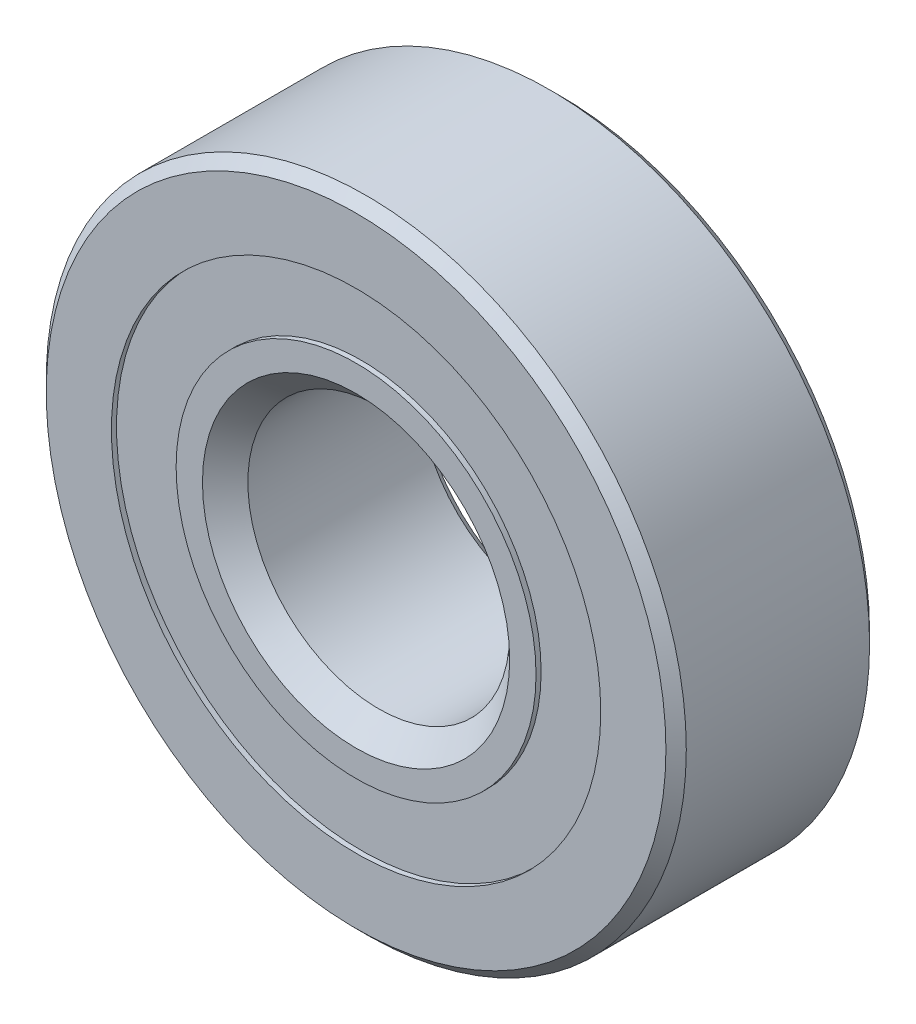
SolidWorks part; units mm, degrees
ref_plane "Front Plane" through (0, 0, 0) normal (0, 0, 1) x (1, 0, 0)
ref_plane "Top Plane" through (0, 0, 0) normal (0, 1, 0) x (1, 0, 0)
ref_plane "Right Plane" through (0, 0, 0) normal (1, 0, 0) x (0, 0, -1)
sketch "Sketch1" plane through (0, 0, 0) normal (1, 0, 0) x (0, 0, -1)
  line L0 (-5.5562, 0) -> (5.5562, 0) construction
  line L1 (0, 17.4625) -> (0, -17.4625) construction
  line L2 (5.0006, 17.4625) -> (-5.0006, 17.4625)
  line L3 (-5.0006, 17.4625) -> (-5.5563, 16.9069)
  line L4 (-5.5563, 16.9069) -> (-5.5563, 13.3498)
  line L5 (-5.5563, 13.3498) -> (-2.4694, 13.3498)
  line L6 (5.5562, 13.3498) -> (2.4694, 13.3498)
  line L7 (5.5562, 16.9069) -> (5.5562, 13.3498)
  line L8 (5.0006, 17.4625) -> (5.5562, 16.9069)
  line L9 (0, 17.4625) -> (0, 12.3031) construction
  line L10 (0, 12.3031) -> (0, 7.1437) construction
  arc A0 (-2.4694, 13.3498) -> (2.4694, 13.3498) centre (0, 12.3031) cw
  point P14 (0, 7.1437)
  dimension "Width" = 11.1125
  dimension "OD" = 34.925
  dimension "D1" = 45
  dimension "D2" = 0.5556
  dimension "D3" = 4.9389
  dimension "D4" = 1.0467
revolve "Revolve1" add sketch "Sketch1" angle 360 about L0
sketch "Sketch2" plane through (0, 0, 0) normal (1, 0, 0) x (0, 0, -1)
  line L0 (-5.2784, 11.2564) -> (-2.4694, 11.2564)
  line L1 (-5.5563, 16.9069) -> (-5.5563, -16.9069) construction
  line L2 (-5.5563, 9.8194) -> (-5.2784, 9.8194) construction
  line L3 (-5.2784, 9.5416) -> (-4.1192, 8.3824)
  line L4 (-4.1192, 8.3824) -> (0, 8.3824)
  line L5 (0, 17.4625) -> (0, -17.4625) construction
  line L6 (0, 8.3824) -> (0, 9.621)
  line L7 (0, 9.621) -> (0, 7.1437) construction
  line L8 (-5.5563, 11.2564) -> (-5.5563, 8.3824) construction
  line L9 (-5.5563, 8.3824) -> (-4.1192, 8.3824) construction
  line L10 (-5.2784, 11.2564) -> (-5.2784, 9.5416)
  line L11 (-5.2784, 11.2564) -> (-5.2784, 17.1847) construction
  line L12 (-5.0006, 17.4625) -> (-5.5563, 16.9069) construction
  arc A0 (-2.4694, 11.2564) -> (0, 9.621) centre (0, 12.3031) ccw
  arc A1 (2.4694, 13.3498) -> (-2.4694, 13.3498) centre (0, 12.3031) ccw construction
  circle A2 centre (0, 12.3031) radius 2.6821 construction
  dimension "D1" = 45
revolve "Revolve2" [suppressed] add sketch "Sketch2" angle 360 about L0
sketch "Sketch3" plane through (0, 0, 0) normal (1, 0, 0) x (0, 0, -1)
  line L0 (-5.2784, 9.5416) -> (-4.1192, 8.3824)
  line L1 (-4.1192, 8.3824) -> (0, 8.3824)
  line L2 (0, 8.3824) -> (0, 9.621)
  line L3 (-5.5563, 9.8194) -> (-5.5563, 8.3824)
  line L4 (-5.5563, 11.2564) -> (-5.5563, 8.3824) construction
  line L5 (-5.5563, 8.3824) -> (-4.3176, 7.1437)
  line L6 (-4.3176, 7.1437) -> (5.0006, 7.1437)
  line L7 (5.0006, 17.4625) -> (5.0006, -17.4625) construction
  line L8 (5.0006, 7.1437) -> (5.5562, 7.6994)
  line L9 (5.5562, -16.9069) -> (5.5562, 16.9069) construction
  line L10 (5.5562, 7.6994) -> (5.5562, 11.2564)
  line L11 (5.5562, 11.2564) -> (2.4694, 11.2564)
  line L12 (-5.5563, 9.8194) -> (-5.2784, 9.8194)
  line L13 (5.0006, 17.4625) -> (5.5562, 16.9069) construction
  line L14 (-5.2784, 9.8194) -> (-5.2784, 9.5416)
  circle A0 centre (0, 12.3031) radius 2.6821 construction
  arc A1 (2.4694, 11.2564) -> (0, 9.621) centre (0, 12.3031) cw
revolve "Revolve3" add sketch "Sketch3" angle 360 about L0
sketch "Sketch4" plane through (0, 0, 0) normal (1, 0, 0) x (0, 0, -1)
  line L0 (-2.6821, 12.3031) -> (2.6821, 12.3031)
  circle A1 centre (0, 12.3031) radius 2.6821 construction
  arc A2 (-2.6821, 12.3031) -> (2.6821, 12.3031) centre (0, 12.3031) cw
  arc A3 (2.4694, 13.3498) -> (-2.4694, 13.3498) centre (0, 12.3031) ccw construction
revolve "Revolve4" add sketch "Sketch4" angle 360 about L0
ref_axis "Axis1" through (0, 0, -5.5562) along (0, 0, 1)
pattern_circular "CirPattern1" count 12 every 30 about axis through (0, 0, -5.5562) along (0, 0, 1) of bodies 104
sketch "Sketch5" plane through (0, 0, 0) normal (1, 0, 0) x (0, 0, -1)
  line L0 (-5.5563, 13.3498) -> (-2.4694, 13.3498) construction
  line L1 (-5.2784, 13.3498) -> (-2.6821, 13.3498)
  line L2 (-5.2784, 13.3498) -> (-5.2784, 9.8194)
  line L3 (-5.2784, 9.8194) -> (-2.6821, 9.8194)
  line L4 (-2.6821, 13.3498) -> (-2.6821, 9.8194)
  line L6 (-5.0006, 17.4625) -> (-5.5563, 16.9069) construction
  line L7 (0, 17.4625) -> (0, 7.1437) construction
  line L8 (5.2784, 9.8194) -> (2.6821, 9.8194)
  line L9 (2.6821, 13.3498) -> (2.6821, 9.8194)
  line L10 (5.2784, 13.3498) -> (2.6821, 13.3498)
  line L11 (5.2784, 13.3498) -> (5.2784, 9.8194)
  circle A0 centre (0, 12.3031) radius 2.6821 construction
  point P10 (-5.2784, 17.1847)
revolve "Revolve5" add sketch "Sketch5" angle 360 about L0
equation "\"D2@Sketch1\" = \"Width@Sketch1\"*.05"
equation "\"D3@Sketch1\" = \"Width@Sketch1\"/2.25"
equation "\"D4@Sketch1\" = (((\"OD@Sketch1\"-\"Width@Sketch1\")/2)/3.25)/3.5"
equation "\"D2@CirPattern1\" = 360/\"Balls@CirPattern1\""
